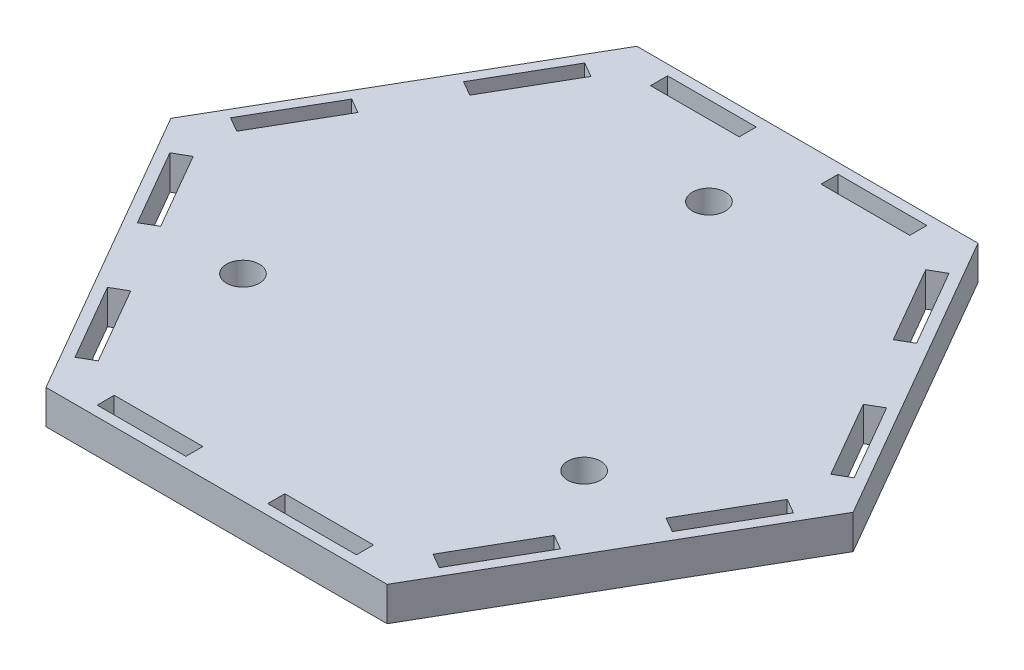
SolidWorks part; units mm, degrees
material "Cedar"
ref_plane "Front Plane" through (0, 0, 0) normal (0, 0, 1) x (1, 0, 0)
ref_plane "Top Plane" through (0, 0, 0) normal (0, 1, 0) x (1, 0, 0)
ref_plane "Right Plane" through (0, 0, 0) normal (1, 0, 0) x (0, 0, -1)
sketch "Sketch1" plane through (0, 0, 0) normal (0, 1, 0) x (1, 0, 0)
  line L0 (-63.5, 0) -> (-31.75, -54.9926)
  line L1 (63.5, 0) -> (31.75, 54.9926)
  line L2 (31.75, 54.9926) -> (-31.75, 54.9926)
  line L3 (-31.75, 54.9926) -> (-63.5, 0)
  line L4 (-31.75, -54.9926) -> (31.75, -54.9926)
  line L5 (31.75, -54.9926) -> (63.5, 0)
  line L6 (0, 0) -> (63.5, 0) construction
  circle A0 centre (0, 0) radius 54.9926 construction
  dimension "D1" = 63.5
extrude "Boss-Extrude1" add sketch "Sketch1" along normal blind 6.35
sketch "Sketch2" plane through (0, 6.35, 0) normal (0, 1, 0) x (1, 0, 0)
  line L0 (0, 0) -> (0, 36.6617) construction
  line L1 (31.75, -18.3309) -> (0, 36.6617) construction
  line L2 (0, 36.6617) -> (-31.75, -18.3309) construction
  line L3 (-31.75, -18.3309) -> (31.75, -18.3309) construction
  line L4 (-60.5671, 5.08) -> (-25.8841, -54.9926) construction
  line L5 (-31.75, 54.9926) -> (-63.5, 0) construction
  line L6 (-31.75, -54.9926) -> (31.75, -54.9926) construction
  line L7 (-63.5, 0) -> (-31.75, -54.9926) construction
  line L8 (-47.625, -27.4963) -> (-43.2256, -24.9563) construction
  line L9 (-55.2906, -4.0591) -> (-58.0402, -5.6466)
  line L10 (-58.0402, -5.6466) -> (-49.7852, -19.9447)
  line L11 (-49.7852, -19.9447) -> (-47.0356, -18.3572)
  line L12 (-47.0356, -18.3572) -> (-55.2906, -4.0591)
  line L13 (-31.1606, -45.8535) -> (-33.9102, -47.441)
  line L14 (-39.4156, -31.5554) -> (-31.1606, -45.8535)
  line L15 (-33.9102, -47.441) -> (-42.1652, -33.1429)
  line L16 (-42.1652, -33.1429) -> (-39.4156, -31.5554)
  line L17 (-25.8841, 54.9926) -> (-60.5671, -5.08) construction
  line L18 (-31.1606, 45.8535) -> (-33.9102, 47.441)
  line L19 (-33.9102, 47.441) -> (-42.1652, 33.1429)
  line L20 (-39.4156, 31.5554) -> (-31.1606, 45.8535)
  line L21 (-42.1652, 33.1429) -> (-39.4156, 31.5554)
  line L22 (-47.625, 27.4963) -> (-43.2256, 24.9563) construction
  line L23 (-49.7852, 19.9447) -> (-47.0356, 18.3572)
  line L24 (-58.0402, 5.6466) -> (-49.7852, 19.9447)
  line L25 (-47.0356, 18.3572) -> (-55.2906, 4.0591)
  line L26 (-55.2906, 4.0591) -> (-58.0402, 5.6466)
  line L27 (34.6829, 49.9126) -> (-34.6829, 49.9126) construction
  line L28 (24.13, 49.9126) -> (24.13, 53.0876)
  line L29 (24.13, 53.0876) -> (7.62, 53.0876)
  line L30 (7.62, 49.9126) -> (24.13, 49.9126)
  line L31 (7.62, 53.0876) -> (7.62, 49.9126)
  line L32 (0, 54.9926) -> (0, 49.9126) construction
  line L33 (-7.62, 53.0876) -> (-7.62, 49.9126)
  line L34 (-24.13, 53.0876) -> (-7.62, 53.0876)
  line L35 (-7.62, 49.9126) -> (-24.13, 49.9126)
  line L36 (-24.13, 49.9126) -> (-24.13, 53.0876)
  line L37 (60.5671, -5.08) -> (25.8841, 54.9926) construction
  line L38 (55.2906, 4.0591) -> (58.0402, 5.6466)
  line L39 (58.0402, 5.6466) -> (49.7852, 19.9447)
  line L40 (47.0356, 18.3572) -> (55.2906, 4.0591)
  line L41 (49.7852, 19.9447) -> (47.0356, 18.3572)
  line L42 (47.625, 27.4963) -> (43.2256, 24.9563) construction
  line L43 (42.1652, 33.1429) -> (39.4156, 31.5554)
  line L44 (33.9102, 47.441) -> (42.1652, 33.1429)
  line L45 (39.4156, 31.5554) -> (31.1606, 45.8535)
  line L46 (31.1606, 45.8535) -> (33.9102, 47.441)
  line L47 (25.8841, -54.9926) -> (60.5671, 5.08) construction
  line L48 (31.1606, -45.8535) -> (33.9102, -47.441)
  line L49 (33.9102, -47.441) -> (42.1652, -33.1429)
  line L50 (39.4156, -31.5554) -> (31.1606, -45.8535)
  line L51 (42.1652, -33.1429) -> (39.4156, -31.5554)
  line L52 (47.625, -27.4963) -> (43.2256, -24.9563) construction
  line L53 (49.7852, -19.9447) -> (47.0356, -18.3572)
  line L54 (58.0402, -5.6466) -> (49.7852, -19.9447)
  line L55 (47.0356, -18.3572) -> (55.2906, -4.0591)
  line L56 (55.2906, -4.0591) -> (58.0402, -5.6466)
  line L57 (-34.6829, -49.9126) -> (34.6829, -49.9126) construction
  line L58 (-24.13, -49.9126) -> (-24.13, -53.0876)
  line L59 (-24.13, -53.0876) -> (-7.62, -53.0876)
  line L60 (-7.62, -49.9126) -> (-24.13, -49.9126)
  line L61 (-7.62, -53.0876) -> (-7.62, -49.9126)
  line L62 (0, -54.9926) -> (0, -49.9126) construction
  line L63 (7.62, -53.0876) -> (7.62, -49.9126)
  line L64 (24.13, -53.0876) -> (7.62, -53.0876)
  line L65 (7.62, -49.9126) -> (24.13, -49.9126)
  line L66 (24.13, -49.9126) -> (24.13, -53.0876)
  circle A0 centre (0, 0) radius 18.3309 construction
  circle A1 centre (-31.75, -18.3309) radius 3.0734
  circle A4 centre (0, 36.6617) radius 3.0734
  circle A5 centre (31.75, -18.3309) radius 3.0734
  point P13 (0, 0)
  point P92 (0, 0)
  point P94 (0, 0)
  dimension "D2" = 6.1468
  dimension "D3" = 3
  dimension "D1" = 63.5
  dimension "D4" = 5.08
  dimension "D5" = 3.175
  dimension "D6" = 16.51
  dimension "D7" = 7.62
  dimension "D8" = 6
extrude "Cut-Extrude1" cut sketch "Sketch2" against normal through all
